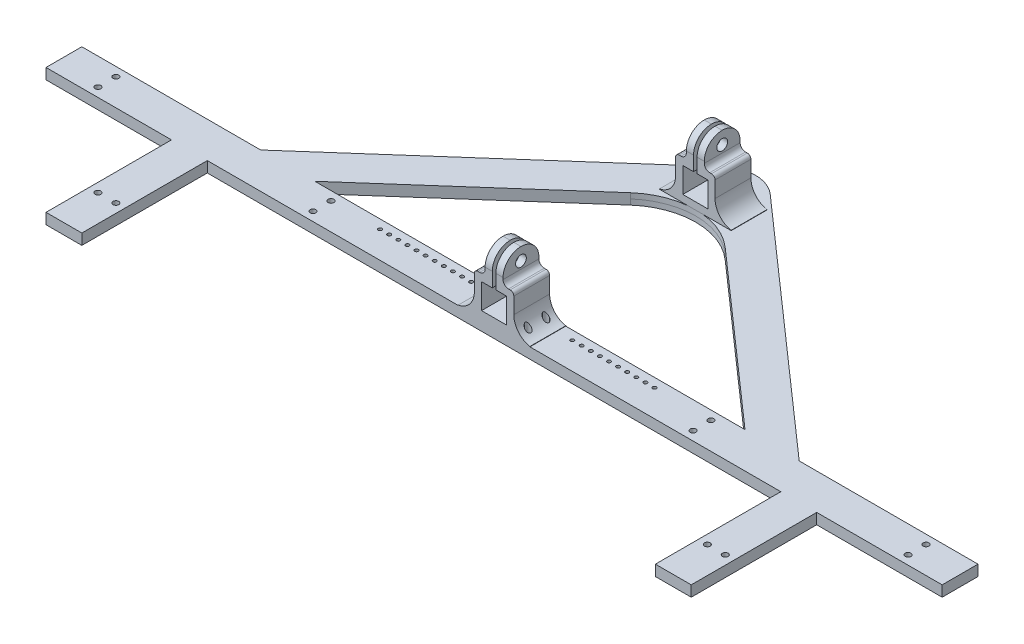
SolidWorks part; units mm, degrees
ref_plane "前视基准面" through (0, 0, 0) normal (0, 0, 1) x (1, 0, 0)
ref_plane "上视基准面" through (0, 0, 0) normal (0, 1, 0) x (1, 0, 0)
ref_plane "右视基准面" through (0, 0, 0) normal (1, 0, 0) x (0, 0, -1)
sketch "草图1" plane through (0, 0, 0) normal (0, 1, 0) x (1, 0, 0)
  line L1 (-125, 5) -> (125, 5)
  line L2 (-125, 5) -> (-125, -5)
  line L3 (-125, -5) -> (125, -5)
  line L4 (125, 5) -> (125, -5)
  line L5 (-125, 5) -> (125, -5) construction
  line L6 (-125, -5) -> (125, 5) construction
  point P0 (0, 0)
  dimension "D1" = 250
  dimension "D2" = 10
extrude "凸台-拉伸1" add sketch "草图1" along normal blind 1.5
sketch "草图22" plane through (0, 0, 0) normal (0, -1, 0) x (1, 0, 0)
  line L0 (0, 107.0541) -> (0, -222.8841) construction
  line L1 (0, 0) -> (-60, 0)
  line L2 (-125, 5) -> (125, 5) construction
  line L4 (125, -5) -> (-125, -5) construction
  line L5 (60, 0) -> (60, -5)
  line L6 (-60, -5) -> (0, -57.915)
  line L7 (0, -57.915) -> (60, -5)
  line L8 (-75.1186, -5) -> (0, -71.2484)
  line L9 (0, -71.2484) -> (75.1186, -5)
  line L10 (-60, -5) -> (-75.1186, -5)
  line L11 (60, -5) -> (75.1186, -5)
  line M16 (-125, -5) -> (125, -5)
  dimension "D1" = 60
  dimension "D2" = 80
  dimension "D3" = 10
extrude "凸台-拉伸10" add sketch "草图22" against normal blind 1.5 separate body contours L0 L6 L8 M16 | L7 L0 L9 M16 region at (33.9206, 0, -34.9152) region at (-33.9206, 0, -34.9152)
fillet "圆角1" radius 10 1 edges at (0, 0.75, -71.2484)
fillet "圆角2" radius 20 1 edges at (0, 0.75, -57.915)
sketch "草图24" plane through (0, 1.5, 0) normal (0, 1, 0) x (1, 0, 0)
  line L1 (-10, 5) -> (10, 5)
  line L2 (-10, 5) -> (-10, -5)
  line L3 (-10, -5) -> (10, -5)
  line L4 (10, 5) -> (10, -5)
  line L5 (-10, 5) -> (10, -5) construction
  line L6 (-10, -5) -> (10, 5) construction
  point P0 (0, 0)
  dimension "D1" = 20
  dimension "D2" = 10
extrude "凸台-拉伸11" add sketch "草图24" along normal blind 20
sketch "草图25" plane through (0, 0, 5) normal (0, 0, 1) x (1, 0, 0)
  line L1 (0, 23.6125) -> (0, -2.2867) construction
sketch "草图26" plane through (0, 1.5, 0) normal (0, 1, 0) x (1, 0, 0)
  line L0 (0, 141.3842) -> (0, -41.294) construction
  line L2 (-11, 61.1419) -> (11, 61.1419)
  line L3 (-11, 61.1419) -> (-11, 51.1419)
  line L4 (-11, 51.1419) -> (11, 51.1419)
  line L5 (11, 61.1419) -> (11, 51.1419)
  line L6 (-11, 61.1419) -> (11, 51.1419) construction
  line L7 (-11, 51.1419) -> (11, 61.1419) construction
  point P6 (0, 56.1419)
  dimension "D1" = 22
  dimension "D2" = 10
extrude "凸台-拉伸12" add sketch "草图26" along normal blind 20
sketch "草图41" plane through (0, 0, 5) normal (0, 0, 1) x (1, 0, 0)
  line L0 (125, 0.75) -> (-129.8236, 0.75) construction
  line L1 (125, 1.5) -> (125, 0) construction
  line L2 (125, 0.75) -> (85, 0.75)
  line L4 (80, 1.5) -> (90, 1.5)
  line L5 (80, 1.5) -> (80, 0)
  line L6 (80, 0) -> (90, 0)
  line L7 (90, 1.5) -> (90, 0)
  line L8 (80, 1.5) -> (90, 0) construction
  line L9 (80, 0) -> (90, 1.5) construction
  line M8 (-125, 0) -> (125, 0)
  line M10 (125, 1.5) -> (10, 1.5)
  dimension "D1" = 40
  dimension "D2" = 10
  dimension "D3" = 1.5
extrude "凸台-拉伸13" add sketch "草图41" along normal blind 35 contours L7 L5 M10 M8 region at (85, 1.3989, 5)
sketch "草图42" plane through (0, 0, 5) normal (0, 0, 1) x (1, 0, 0)
  line L0 (-125, 0.75) -> (-85, 0.75)
  line L1 (-125, 1.5) -> (-125, 0) construction
  line L3 (-90, 1.5) -> (-80, 1.5)
  line L4 (-90, 1.5) -> (-90, 0)
  line L5 (-90, 0) -> (-80, 0)
  line L6 (-80, 1.5) -> (-80, 0)
  line L7 (-90, 1.5) -> (-80, 0) construction
  line L8 (-90, 0) -> (-80, 1.5) construction
  line M14 (-10, 1.5) -> (-125, 1.5)
  line M16 (-125, 0) -> (80, 0)
  dimension "D1" = 40
  dimension "D2" = 10
  dimension "D3" = 1.5
extrude "凸台-拉伸14" add sketch "草图42" along normal blind 35 contours L6 L4 M14 M16 region at (-85, 1.3989, 5)
sketch "草图53" plane through (0, 0, 5) normal (0, 0, 1) x (1, 0, 0)
  line L0 (0, 23.6125) -> (0, -2.2867) construction
  line L1 (0, 23.6125) -> (0, -2.2867) construction
  line L2 (-2.5, 10.5) -> (-0.5, 10.5)
  line L3 (0.5, 10.5) -> (2.5, 10.5)
  line L6 (-2.5, 10.5) -> (2.5, 5.5) construction
  line L7 (-2.5, 5.5) -> (2.5, 10.5) construction
  line L8 (-80, 0) -> (80, 0) construction
  line L10 (-11, 1.5) -> (-5.2878, 1.5)
  line L11 (-11, 1.5) -> (-2.0613, 1.5) construction
  line L12 (-4.5, 12.5) -> (4.5, 12.5)
  line L14 (-1, 19.5) -> (-2.5, 19.5)
  line L15 (-2.5, 19.5) -> (-2.5, 12.5)
  line L17 (1, 19.5) -> (2.5, 19.5)
  line L18 (2.5, 19.5) -> (2.5, 12.5)
  line L22 (-10, 21.5) -> (-11, 21.5)
  line L23 (-11, 21.5) -> (-11, 1.5)
  line L24 (-11, 1.5) -> (-10, 1.5)
  line L25 (-10, 1.5) -> (-10, 21.5)
  line L26 (11, 21.5) -> (10, 21.5)
  line L27 (10, 21.5) -> (10, 1.5)
  line L28 (10, 1.5) -> (11, 1.5)
  line L29 (11, 21.5) -> (11, 1.5)
  line L30 (-1, 19.5) -> (-0.5, 19.5)
  line L31 (1, 19.5) -> (0.5, 19.5)
  line L32 (-0.5, 19.5) -> (-0.5, 10.5)
  line L33 (0.5, 19.5) -> (0.5, 10.5)
  line L34 (-2.5, 10.5) -> (-3.5, 10.5)
  line L35 (2.5, 10.5) -> (3.5, 10.5)
  line L36 (-4.5, 12.5) -> (-5.5, 12.5)
  line L37 (4.5, 12.5) -> (5.5, 12.5)
  line L38 (-3.5, 10.5) -> (-3.5, 3.5)
  line L39 (3.5, 10.5) -> (3.5, 3.5)
  line L40 (-3.5, 3.5) -> (3.5, 3.5)
  line L41 (-5.5, 12.5) -> (-5.5, 7)
  line L42 (5.5, 12.5) -> (5.5, 7)
  arc A0 (-11, 1.5) -> (-5.5, 7) centre (-11, 7) ccw
  arc A1 (11, 1.5) -> (5.5, 7) centre (11, 7) cw
  point P0 (0, 8)
  point P31 (0, 12.5)
  line M7 (10, 21.5) -> (-10, 21.5)
  line M8 (-10, 21.5) -> (-10, 1.5)
  dimension "D1" = 8
  dimension "D5" = 2
  dimension "D2" = 5
  dimension "D3" = 5
  dimension "D8" = 1.5
  dimension "D9" = 0.5
  dimension "D10" = 0.5
  dimension "D11" = 1
  dimension "D12" = 1
  dimension "D13" = 1
  dimension "D15" = 7
  dimension "D16" = 7
sketch "草图57" plane through (0, 0, 0) normal (0, -1, 0) x (-1, 0, 0)
  line L0 (125, -5) -> (90, -5)
  line L1 (90, -5) -> (90, -40)
  line L2 (90, -40) -> (80, -40)
  line L3 (80, -40) -> (80, -5)
  line L4 (80, -5) -> (-80, -5)
  line L5 (-80, -5) -> (-80, -40)
  line L6 (-80, -40) -> (-90, -40)
  line L7 (-90, -40) -> (-90, -5)
  line L8 (-90, -5) -> (-125, -5)
  line L9 (-125, -5) -> (-125, 5)
  line L10 (-125, 5) -> (-75.1186, 5)
  line L11 (-75.1186, 5) -> (-6.6144, 65.415)
  line L12 (-6.6144, 65.415) -> (0, 71.2484)
  line L13 (0, 71.2484) -> (6.6144, 65.415)
  line L14 (6.6144, 65.415) -> (75.1186, 5)
  line L15 (75.1186, 5) -> (125, 5)
  line L16 (125, 5) -> (125, -5)
  line L17 (60, 5) -> (-60, 5)
  line L18 (-60, 5) -> (0, 57.915)
  line L19 (0, 57.915) -> (60, 5)
extrude "凸台-拉伸15" add sketch "草图57" along normal blind 1.5
fillet "圆角5" radius 20 1 edges at (0, -0.75, -57.915)
fillet "圆角6" radius 10 1 edges at (0, -0.75, -71.2484)
sketch "草图58" plane through (0, -1.5, 0) normal (0, -1, 0) x (1, 0, 0)
  line L0 (0, 12.1149) -> (0, -11.1082) construction
  line L1 (0, 0) -> (7, 0)
  line L2 (7, 0) -> (7, 2.5)
  line L3 (7, 0) -> (7, -2.5)
  line L4 (127.0686, 0) -> (101.0767, 0) construction
  line L5 (125, 0) -> (113, 0)
  line L6 (125, -5) -> (125, 5) construction
  line L7 (113, 0) -> (113, 2.5)
  line L8 (113, 0) -> (113, -2.5)
  line L9 (-125, 5) -> (-125, -5) construction
  line L10 (-125, 5) -> (-125, -5)
  line L11 (125, 5) -> (125, -5)
  line L12 (0, 0) -> (53, 0)
  line L14 (53, 0) -> (53, 2.5)
  line L15 (53, 0) -> (53, -2.5)
  line L16 (-85, 40) -> (-85, 28)
  line L17 (-80, 40) -> (-90, 40) construction
  line L18 (-85, 28) -> (-87.5, 28)
  line L19 (-85, 28) -> (-82.5, 28)
  circle A0 centre (7, -2.5) radius 0.8
  circle A1 centre (7, 2.5) radius 0.8
  circle A2 centre (113, 2.5) radius 0.8
  circle A3 centre (113, -2.5) radius 0.8
  circle A4 centre (-113, -2.5) radius 0.8
  circle A5 centre (-113, 2.5) radius 0.8
  circle A6 centre (53, 2.5) radius 0.8
  circle A7 centre (53, -2.5) radius 0.8
  circle A8 centre (-53, -2.5) radius 0.8
  circle A9 centre (-53, 2.5) radius 0.8
  circle A10 centre (-82.5, 28) radius 0.8
  circle A11 centre (-87.5, 28) radius 0.8
  circle A12 centre (82.5, 28) radius 0.8
  circle A13 centre (87.5, 28) radius 0.8
  point P23 (-125, 0)
  dimension "D4" = 1.6
  dimension "D5" = 1.6
  dimension "D9" = 1.6
  dimension "D10" = 1.6
  dimension "D15" = 1.6
  dimension "D16" = 1.6
  dimension "D20" = 1.6
  dimension "D21" = 1.6
  dimension "D1" = 7
  dimension "D2" = 2.5
  dimension "D3" = 2.5
  dimension "D6" = 12
  dimension "D7" = 2.5
  dimension "D8" = 2.5
  dimension "D11" = 250
  dimension "D12" = 53
  dimension "D13" = 2.5
  dimension "D14" = 2.5
  dimension "D17" = 12
  dimension "D18" = 2.5
  dimension "D19" = 2.5
extrude "切除-拉伸52" cut sketch "草图58" against normal through all contours A5 | A4 | A11 | A10 | A9 | A8 | A0 | A1 | A6 | A7 | A2 | A3 | A12 | A13 region at (6.4503, -1.5, 3.0497) region at (7.5497, -1.5, -1.9503) region at (52.4503, -1.5, 3.0497) region at (53.5497, -1.5, -1.9503) region at (112.4503, -1.5, 3.0497) region at (113.5497, -1.5, -1.9503) region at (-88.2774, -1.5, 28) region at (-82.5, -1.5, 28.7774) region at (-113, -1.5, -2.5) region at (-113, -1.5, 2.5) region at (-53, -1.5, -2.5) region at (-53, -1.5, 2.5) region at (82.5, -1.5, 28) region at (87.5, -1.5, 28)
extrude "切除-拉伸53" cut sketch "草图53" against normal through all contours A1 L27 A0 L41 L36 L12 L15 L14 L30 L32 L33 L31 L17 L18 L37 L42 M7 M8 | L38 L40 L39 L35 L3 L33 L12 L32 L2 L34 | L24 L25 L22 L23 | L29 L26 L27 L28 region at (0, 7.1765, 5) region at (0, 13.7336, 5)
fillet "圆角7" radius 5 8 edges at (-1.5, 19.5, -51.1419) (-1.5, 19.5, -61.1419) (1.5, 19.5, -61.1419) (1.5, 19.5, -51.1419) (-1.5, 19.5, 5) (-1.5, 19.5, -5) (1.5, 19.5, -5) (1.5, 19.5, 5)
sketch "草图59" plane through (2.5, 0, 0) normal (1, 0, 0) x (0, 0, -1)
  line L0 (0, 19.5) -> (0, 16)
  circle A0 centre (0, 16) radius 1.5
  dimension "D2" = 3
  dimension "D1" = 3.5
extrude "切除-拉伸54" cut sketch "草图59" against normal through all contours A0 region at (2.5, 14.9693, 1.0307)
sketch "草图60" plane through (2.5, 0, 0) normal (1, 0, 0) x (0, 0, -1)
  line L0 (56.1419, 19.5) -> (56.1419, 16)
  circle A0 centre (56.1419, 16) radius 1.5
  dimension "D2" = 3
  dimension "D1" = 3.5
extrude "切除-拉伸55" cut sketch "草图60" against normal through all contours A0 region at (2.5, 14.9693, -55.1112)
fillet "圆角8" radius 1.5 4 edges at (-2.5, 12.5, -56.1419) (2.5, 12.5, -56.1419) (-2.5, 12.5, 0) (2.5, 12.5, 0)
fillet "圆角9" radius 1 4 edges at (-5.5, 12.5, -56.1419) (5.5, 12.5, -56.1419) (-5.5, 12.5, 0) (5.5, 12.5, 0)
sketch "草图61" plane through (0, 1.5, 0) normal (0, 1, 0) x (1, 0, 0)
  line L0 (7.8, 2.5) -> (53.8, 2.5)
  line L1 (53, 2.5) -> (41, 2.5)
  line L2 (-52.2, 2.5) -> (-8.5647, 2.5)
  line L3 (-53, 2.5) -> (-41, 2.5)
  circle A0 centre (7, 2.5) radius 0.8 construction
  circle A1 centre (53, 2.5) radius 0.8 construction
  circle A2 centre (14.3, 2.5) radius 0.5
  circle A3 centre (16.94, 2.5) radius 0.5
  circle A4 centre (19.48, 2.5) radius 0.5
  circle A5 centre (22.02, 2.5) radius 0.5
  circle A6 centre (24.56, 2.5) radius 0.5
  circle A7 centre (27.1, 2.5) radius 0.5
  circle A8 centre (29.64, 2.5) radius 0.5
  circle A9 centre (32.18, 2.5) radius 0.5
  circle A10 centre (34.72, 2.5) radius 0.5
  circle A11 centre (37.26, 2.5) radius 0.5
  circle A12 centre (-53, 2.5) radius 0.8 construction
  circle A13 centre (-39.3, 2.5) radius 0.5
  circle A14 centre (-36.76, 2.5) radius 0.5
  circle A15 centre (-34.22, 2.5) radius 0.5
  circle A16 centre (-31.68, 2.5) radius 0.5
  circle A17 centre (-29.14, 2.5) radius 0.5
  circle A18 centre (-26.6, 2.5) radius 0.5
  circle A19 centre (-24.06, 2.5) radius 0.5
  circle A20 centre (-21.52, 2.5) radius 0.5
  circle A21 centre (-18.98, 2.5) radius 0.5
  circle A22 centre (-16.44, 2.5) radius 0.5
  circle A23 centre (-13.9, 2.5) radius 0.5
  circle A24 centre (-11.36, 2.5) radius 0.5
  dimension "D1" = 1
  dimension "D2" = 1
  dimension "D3" = 2.64
  dimension "D4" = 1
  dimension "D5" = 2.54
  dimension "D6" = 1
  dimension "D7" = 2.54
  dimension "D8" = 1
  dimension "D9" = 2.54
  dimension "D10" = 1
  dimension "D12" = 1
  dimension "D14" = 1
  dimension "D16" = 1
  dimension "D18" = 1
  dimension "D23" = 1
  dimension "D24" = 1
  dimension "D26" = 1
  dimension "D28" = 1
  dimension "D30" = 1
  dimension "D32" = 1
  dimension "D34" = 1
  dimension "D36" = 1
  dimension "D38" = 1
  dimension "D40" = 1
  dimension "D42" = 1
  dimension "D44" = 1
  dimension "D11" = 2.54
  dimension "D13" = 2.54
  dimension "D15" = 2.54
  dimension "D17" = 2.54
  dimension "D19" = 2.54
  dimension "D20" = 12
  dimension "D21" = 6.5
  dimension "D22" = 12
  dimension "D25" = 2.54
  dimension "D27" = 2.54
  dimension "D29" = 2.54
  dimension "D31" = 2.54
  dimension "D33" = 2.54
  dimension "D35" = 2.54
  dimension "D37" = 2.54
  dimension "D39" = 2.54
  dimension "D41" = 2.54
  dimension "D43" = 2.54
  dimension "D45" = 2.54
  dimension "D46" = 1.7
  dimension "D47" = 0
extrude "切除-拉伸56" cut sketch "草图61" against normal through all contours L2 A13 | L2 A13 | L2 A14 | L2 A14 | L2 A15 | L2 A15 | L2 A16 | L2 A16 | L2 A17 | L2 A17 | L2 A18 | L2 A18 | L2 A19 | L2 A19 | L2 A20 | L2 A20 | L2 A21 | L2 A21 | L2 A22 | L2 A22 | L2 A23 | L2 A23 | L2 A24 | L2 A24 | L0 A2 | L0 A2 | L0 A3 | L0 A3 | L0 A4 | L0 A4 | L0 A5 | L0 A5 | L0 A6 | L0 A6 | L0 A7 | L0 A7 | L0 A8 | L0 A8 | L0 A9 | L0 A9 | L0 A10 | L0 A10 | L0 A11 | L0 A11 region at (14.3, 1.5, -2.7122) region at (37.26, 1.5, -2.7122) region at (37.26, 1.5, -2.2878) region at (34.72, 1.5, -2.7122) region at (34.72, 1.5, -2.2878) region at (32.18, 1.5, -2.7122) region at (32.18, 1.5, -2.2878) region at (29.64, 1.5, -2.7122) region at (29.64, 1.5, -2.2878) region at (27.1, 1.5, -2.7122) region at (27.1, 1.5, -2.2878) region at (24.56, 1.5, -2.7122) region at (24.56, 1.5, -2.2878) region at (22.02, 1.5, -2.7122) region at (22.02, 1.5, -2.2878) region at (19.48, 1.5, -2.7122) region at (19.48, 1.5, -2.2878) region at (16.94, 1.5, -2.7122) region at (16.94, 1.5, -2.2878) region at (14.3, 1.5, -2.2878) region at (-39.3, 1.5, -2.7122) region at (-11.36, 1.5, -2.7122) region at (-11.36, 1.5, -2.2878) region at (-13.9, 1.5, -2.7122) region at (-13.9, 1.5, -2.2878) region at (-16.44, 1.5, -2.7122) region at (-16.44, 1.5, -2.2878) region at (-18.98, 1.5, -2.7122) region at (-18.98, 1.5, -2.2878) region at (-21.52, 1.5, -2.7122) region at (-21.52, 1.5, -2.2878) region at (-24.06, 1.5, -2.7122) region at (-24.06, 1.5, -2.2878) region at (-26.6, 1.5, -2.7122) region at (-26.6, 1.5, -2.2878) region at (-29.14, 1.5, -2.7122) region at (-29.14, 1.5, -2.2878) region at (-31.68, 1.5, -2.7122) region at (-31.68, 1.5, -2.2878) region at (-34.22, 1.5, -2.7122) region at (-34.22, 1.5, -2.2878) region at (-36.76, 1.5, -2.7122) region at (-36.76, 1.5, -2.2878) region at (-39.3, 1.5, -2.2878)
